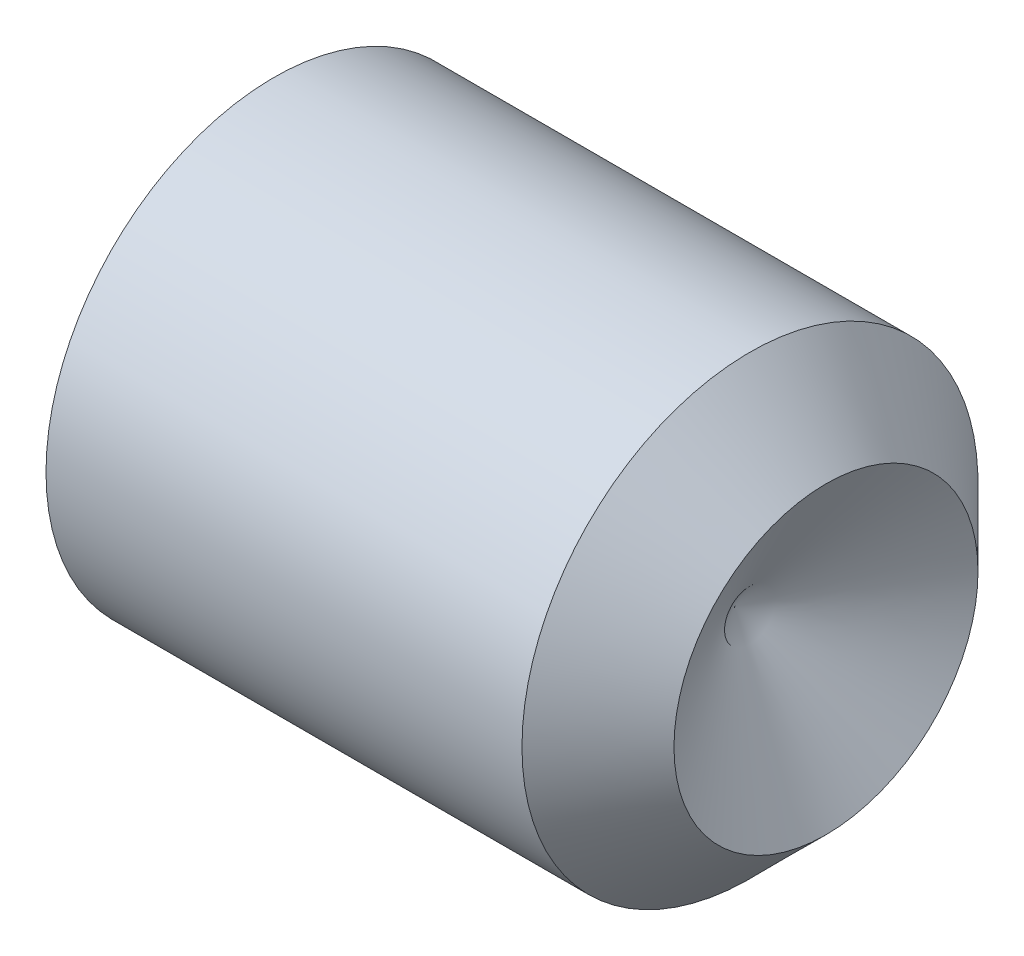
SolidWorks part; units mm, degrees
revolve "BaseBody" add sketch "BodySke" angle 360 about L5 other way angle 60
sketch "BodySke" plane through (0, 0, 0) normal (0, 0, 1) x (1, 0, 0)
  line L0 (0, 0) -> (0, 10.352)
  line L1 (0, 10.352) -> (0.9515, 12)
  line L2 (0.9515, 12) -> (26, 12)
  line L3 (26, 12) -> (30, 8)
  line L4 (25.1931, 0) -> (0, 0)
  line L5 (-12.7, 0) -> (88.9, 0) construction
  line L6 (25.1931, 0) -> (30, 8)
  line L7 (30, 8) -> (30, 17.525) construction
  line L8 (0, -10.352) -> (0.9515, -12) construction
  line L9 (25.1931, 0) -> (30, -8) construction
  line L10 (26, -12) -> (30, -8) construction
  line L11 (3, 15.875) -> (3, -3.175) construction
  dimension "Length" = 30
  dimension "Diameter" = 24
cosmetic thread "ThreadCosmetic" [suppressed] parameters "Thread_minor"=20.704
ref_plane "Plane1" through (0, 0, 0) normal (0, 0, 1) x (1, 0, 0)
ref_plane "Plane2" through (0, 0, 0) normal (0, 1, 0) x (1, 0, 0)
ref_plane "Plane3" through (0, 0, 0) normal (1, 0, 0) x (0, 0, -1)
sketch "Sketch2" plane through (0, 0, 0) normal (-1, 0, 0) x (0, 0, 1)
  line L0 (3.4641, 6) -> (-3.4641, 6)
  line L1 (-3.4641, 6) -> (-6.9282, 0)
  line L2 (3.4641, 6) -> (6.9282, 0)
  line L3 (3.4641, -6) -> (6.9282, 0)
  line L4 (3.4641, -6) -> (-3.4641, -6)
  line L5 (-3.4641, -6) -> (-6.9282, 0)
  dimension "D2" = 6
  dimension "D3" = 6
extrude "Hex" [suppressed] cut sketch "Sketch2" against normal blind 12
sketch "Sketch4" plane through (0, 4.7709, -0.5249) normal (-1, 0, 0) x (0, 0, 1)
  line L0 (0.5249, -4.7709) -> (8.1959, -4.7709)
  line L1 (0.5249, -4.7709) -> (6.6732, -1.2211) construction
  line L2 (0.5249, -4.7709) -> (4.3604, 1.8724)
  line L3 (6.7899, -3.1774) -> (7.8687, -2.5545)
  line L4 (5.0374, -0.142) -> (6.1162, 0.4809)
  arc A0 (6.7899, -3.1774) -> (5.0374, -0.142) centre (0.5249, -4.7709) ccw
  arc A1 (8.1959, -4.7709) -> (7.8687, -2.5545) centre (0.5249, -4.7709) ccw
  arc A2 (4.3604, 1.8724) -> (6.1162, 0.4809) centre (0.5249, -4.7709) cw
  circle A3 centre (0.5249, -4.7709) radius 6.4645 construction
  circle A4 centre (0.5249, -4.7709) radius 7.671 construction
  dimension "Spline_n_dim" = 12.929
  dimension "Spline_m_dim" = 15.342
  dimension "D1" = 30
  dimension "Spline_p_dim" = 3.505
  dimension "D3" = 1.7525
extrude "Spline6" [suppressed] cut sketch "Sketch4" against normal blind 12
pattern_circular "CirPattern1" [suppressed] count 6 every 60 about axis through (-12.7, 0, 0) along (1, 0, 0)
sketch "Sketch5" plane through (0, 1.5227, 6.1981) normal (-1, 0, 0) x (0, 0, 1)
  line L0 (-6.1981, -1.5227) -> (1.4729, -1.5227)
  line L1 (-6.1981, -1.5227) -> (-1.178, 3.4975) construction
  line L2 (-6.1981, -1.5227) -> (-6.1981, 6.1483)
  line L3 (-0.3878, 1.8092) -> (0.3219, 2.5189)
  line L4 (-2.8662, 4.2876) -> (-2.1565, 4.9973)
  line L5 (-2.8662, 4.2876) -> (-0.3878, 1.8092)
  arc A1 (1.4729, -1.5227) -> (0.3219, 2.5189) centre (-6.1981, -1.5227) ccw
  arc A2 (-6.1981, 6.1483) -> (-2.1565, 4.9973) centre (-6.1981, -1.5227) cw
  circle A3 centre (-6.1981, -1.5227) radius 6.4645 construction
  circle A4 centre (-6.1981, -1.5227) radius 7.671 construction
  dimension "Spline_n_dim" = 12.929
  dimension "Spline_m_dim" = 15.342
  dimension "Spline_p_dim" = 3.505
  dimension "D3" = 1.7525
  dimension "D1" = 45
  dimension "Spline_a_dim" = 90
extrude "Spline4" cut sketch "Sketch5" against normal blind 12
pattern_circular "CirPattern2" count 4 every 90 about axis through (-12.7, 0, 0) along (1, 0, 0) of "Spline4"
sketch "ThdSchSke" plane through (0, 0, 0) normal (0, 0, 1) x (1, 0, 0)
  line L0 (0.9515, -10.352) -> (-0.2025, -12)
  line L1 (0.9515, -10.352) -> (2.1054, -12)
  line L2 (2.1054, -12) -> (2.1054, -15)
  line L3 (-3.175, 0) -> (5.1513, 0) construction
  line L4 (0.9515, 12) -> (0.9515, -12) construction
  line L5 (2.1054, -15) -> (-0.2025, -15)
  line L6 (-0.2025, -15) -> (-0.2025, -12)
  dimension "Thread_minor" = 20.704
  dimension "Diameter" = 24
revolve "ThreadSchematic" [suppressed] cut sketch "ThdSchSke" angle 360 about L3
pattern_linear "ThdSchPat" [suppressed]
equation "\"D2@Sketch2\" = \"Hex_size@Sketch2\" / 2"
equation "\"D3@Sketch2\" = \"Hex_size@Sketch2\" / 2"
equation "\"Thread_minor@ThreadCosmetic\" = \"Minor_dia@BodySke\""
equation "\"D1@Sketch4\" = \"Spline_a_dim@Sketch4\" / 2"
equation "\"D3@Sketch4\" = \"Spline_p_dim@Sketch4\" / 2"
equation "\"D2@CirPattern1\" = \"Spline_a_dim@Sketch4\""
equation "\"Num_teeth@CirPattern1\" = 360 / \"D2@CirPattern1\""
equation "\"Spline_a_dim@Sketch5\" = 90"
equation "\"Spline_p_dim@Sketch5\" = \"Spline_p_dim@Sketch4\""
equation "\"Spline_m_dim@Sketch5\" = \"Spline_m_dim@Sketch4\""
equation "\"Spline_n_dim@Sketch5\" = \"Spline_n_dim@Sketch4\""
equation "\"D1@Sketch5\" = \"Spline_a_dim@Sketch5\" / 2"
equation "\"D3@Sketch5\" = \"Spline_p_dim@Sketch5\" / 2"
equation "\"Key_eng@Spline4\" = \"Key_eng@Spline6\""
equation "\"Thread_minor@ThdSchSke\" = \"Thread_minor@ThreadCosmetic\""
equation "\"Diameter@ThdSchSke\" = \"Diameter@BodySke\""
equation "\"Overcut@ThdSchSke\" = \"Diameter@BodySke\" * 1.25"
equation "\"Num_threads@ThdSchPat\" = int( (\"Length@BodySke\" - ( ( ( \"Diameter@BodySke\" - \"Minor_dia@BodySke\" ) * 0.5 ) / tan( \"Drive_ch_ang@BodySke\" * 0.017453292 ) ) - ( ( ( \"Diameter@BodySke\" - \"Cup_dia@BodySke\" ) * 0.5 ) * tan( \"Cup_nose_ang@BodySke\" * 0.017453292 ) ) ) / \"Advance@BodySke\" + 0.999 )  + 1"
equation "\"Advance@ThdSchPat\" = (\"Length@BodySke\" - ( ( ( \"Diameter@BodySke\" - \"Minor_dia@BodySke\" ) * 0.5 ) / tan( \"Drive_ch_ang@BodySke\" * 0.017453292 ) ) - ( ( ( \"Diameter@BodySke\" - \"Cup_dia@BodySke\" ) * 0.5 ) * tan( \"Cup_nose_ang@BodySke\" * 0.017453292 ) ) ) /  (\"Num_threads@ThdSchPat\" - 1) 'relax it"
equation "' \"Num_threads@ThdSchPat\" = \"Num_threads@ThdSchPat\" - sgn( \"Num_threads@ThdSchPat\" - 1) '---chamfered tips only---"
